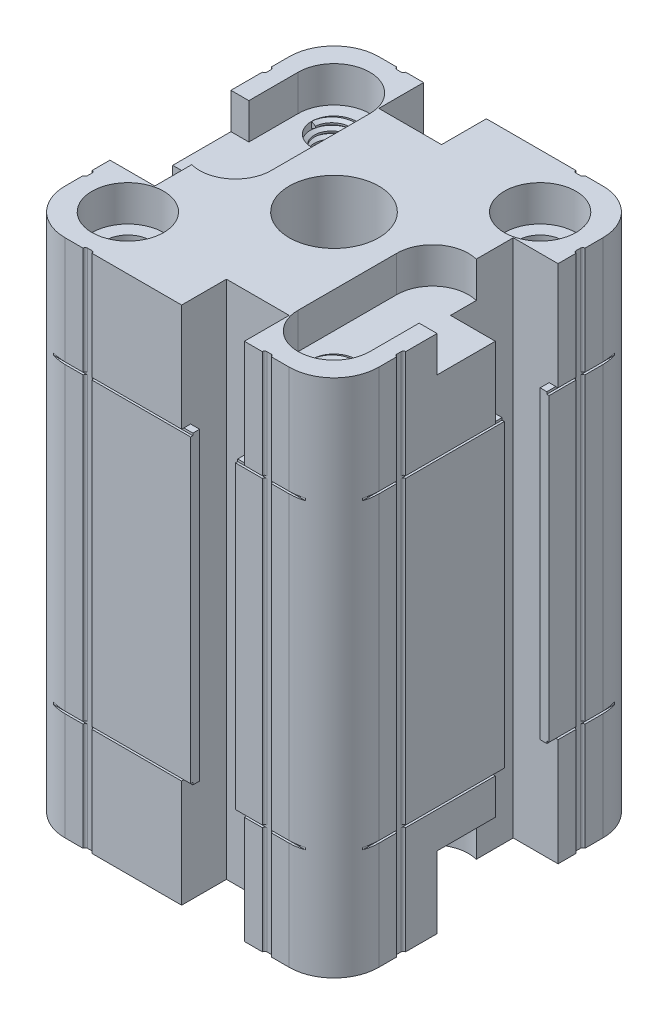
SolidWorks part; units mm, degrees
ref_plane "Front Plane" through (0, 0, 0) normal (0, 0, 1) x (1, 0, 0)
ref_plane "Top Plane" through (0, 0, 0) normal (0, 1, 0) x (1, 0, 0)
ref_plane "Right Plane" through (0, 0, 0) normal (1, 0, 0) x (0, 0, -1)
sketch "Sketch1" plane through (0, 0, 0) normal (0, 1, 0) x (1, 0, 0)
  line L1 (0, 0) -> (35, 0)
  line L2 (0, 0) -> (0, 35)
  line L3 (0, 35) -> (35, 35)
  line L4 (35, 0) -> (35, 35)
  dimension "D1" = 35
  dimension "D2" = 35
extrude "Boss-Extrude1" add sketch "Sketch1" along normal blind 58
sketch "Sketch2" plane through (0, 0, 0) normal (0, -1, 0) x (-1, 0, 0)
  line L0 (0, 0) -> (-35, 0) construction
  line L1 (0, 35) -> (0, 0) construction
  line L2 (-29, 6) -> (-29, 17) construction
  line L3 (-33, 6) -> (-33, 17)
  line L4 (-25, 6) -> (-25, 17)
  line L5 (-35, 0) -> (-35, 35) construction
  line L6 (-35, 35) -> (0, 35) construction
  line L7 (-6, 18) -> (-6, 29) construction
  line L8 (-10, 18) -> (-10, 29)
  line L9 (-2, 18) -> (-2, 29)
  circle A0 centre (-6, 6) radius 4
  circle A1 centre (-29, 29) radius 4
  arc A2 (-33, 6) -> (-25, 6) centre (-29, 6) ccw
  arc A3 (-25, 17) -> (-33, 17) centre (-29, 17) ccw
  arc A4 (-10, 18) -> (-2, 18) centre (-6, 18) ccw
  arc A5 (-2, 29) -> (-10, 29) centre (-6, 29) ccw
  point P10 (-29, 11.5)
  point P21 (-6, 23.5)
  dimension "D1" = 8
  dimension "D4" = 4
  dimension "D5" = 11
  dimension "D10" = 4
  dimension "D11" = 6
  dimension "D2" = 6
  dimension "D3" = 6
  dimension "D6" = 6
  dimension "D7" = 6
  dimension "D8" = 6
  dimension "D9" = 11
extrude "Cut-Extrude1" cut sketch "Sketch2" against normal blind 8
sketch "Sketch3" plane through (0, 0, 0) normal (0, -1, 0) x (-1, 0, 0)
  line L0 (0, 35) -> (0, 0) construction
  line L1 (-5, 23.5) -> (0, 23.5)
  line L2 (-5, 23.5) -> (-5, 14.127)
  line L3 (-5, 14.127) -> (0, 14.127)
  line L4 (0, 23.5) -> (0, 14.127)
  line L5 (-2, 18) -> (-2, 29) construction
  line L6 (-35, 20.873) -> (-30, 20.873)
  line L7 (-35, 20.873) -> (-35, 11.5)
  line L8 (-35, 11.5) -> (-30, 11.5)
  line L9 (-30, 20.873) -> (-30, 11.5)
  line L10 (-35, 0) -> (-35, 35) construction
  line L11 (-33, 17) -> (-33, 6) construction
  arc A2 (-25, 17) -> (-33, 17) centre (-29, 17) ccw construction
  arc A3 (-10, 18) -> (-2, 18) centre (-6, 18) ccw construction
  point P13 (-2, 23.5)
  point P25 (-32.5, 20.873)
  point P34 (-33, 11.5)
  dimension "D1" = 5
  dimension "D2" = 5
extrude "Cut-Extrude2" cut sketch "Sketch3" against normal up to surface (8 mm away) up to face at (6, 8, -23.5)
sketch "Sketch5" plane through (0, 0, 0) normal (0, -1, 0) x (1, 0, 0)
  line L0 (35, -20.873) -> (35, -35) construction
  line L1 (5, -17) -> (0, -17)
  line L2 (5, -17) -> (5, -10)
  line L3 (5, -10) -> (0, -10)
  line L4 (0, -17) -> (0, -10)
  line L5 (30, -18) -> (35, -18)
  line L6 (30, -18) -> (30, -25)
  line L7 (30, -25) -> (35, -25)
  line L8 (35, -18) -> (35, -25)
  line L9 (0, 0) -> (35, 0) construction
  line L10 (18, 0) -> (25, 0)
  line L11 (18, 0) -> (18, -5)
  line L12 (18, -5) -> (25, -5)
  line L13 (25, 0) -> (25, -5)
  line L14 (35, -35) -> (0, -35) construction
  line L15 (10, -35) -> (17, -35)
  line L16 (10, -35) -> (10, -30)
  line L17 (10, -30) -> (17, -30)
  line L18 (17, -35) -> (17, -30)
  circle A0 centre (6, -6) radius 4 construction
  circle A1 centre (29, -29) radius 4 construction
  dimension "D1" = 7
  dimension "D2" = 7
  dimension "D3" = 5
  dimension "D4" = 7
  dimension "D5" = 10
  dimension "D6" = 7
  dimension "D7" = 5
  dimension "D8" = 10
extrude "Cut-Extrude3" cut sketch "Sketch5" against normal blind 12
sketch "Sketch6" plane through (0, 12, 0) normal (0, -1, 0) x (1, 0, 0)
  line L6 (0, -16) -> (1, -16)
  line L7 (0, -10) -> (0, -17) construction
  line L8 (1, -16) -> (1, -17)
  line L9 (0, -17) -> (5, -17) construction
  line L10 (1, -17) -> (5, -17)
  line L11 (5, -17) -> (5, -10)
  line L12 (5, -10) -> (1, -10)
  line L13 (5, -10) -> (0, -10) construction
  line L14 (1, -10) -> (1, -11)
  line L15 (1, -11) -> (0, -11)
  line L16 (0, -11) -> (0, -16)
  line L17 (19, 0) -> (19, -1)
  line L18 (25, 0) -> (18, 0) construction
  line L19 (19, -1) -> (18, -1)
  line L20 (18, 0) -> (18, -5) construction
  line L21 (18, -1) -> (18, -5)
  line L22 (18, -5) -> (25, -5)
  line L23 (25, -5) -> (25, -1.01)
  line L24 (25, -5) -> (25, 0) construction
  line L25 (25, -1.01) -> (24, -1.01)
  line L26 (24, -1.01) -> (24, 0)
  line L27 (24, 0) -> (19, 0)
  line L28 (35, -19) -> (34, -19)
  line L29 (35, -25) -> (35, -18) construction
  line L30 (34, -19) -> (34, -18)
  line L31 (35, -18) -> (30, -18) construction
  line L32 (34, -18) -> (30, -18)
  line L33 (30, -18) -> (30, -25)
  line L34 (30, -25) -> (34, -25)
  line L35 (30, -25) -> (35, -25) construction
  line L36 (34, -25) -> (34, -24)
  line L37 (34, -24) -> (35, -24)
  line L38 (35, -24) -> (35, -19)
  line L39 (11, -35) -> (11, -34)
  line L40 (10, -35) -> (17, -35) construction
  line L41 (11, -34) -> (10, -34)
  line L42 (10, -30) -> (10, -35) construction
  line L43 (10, -34) -> (10, -30)
  line L44 (10, -30) -> (17, -30)
  line L45 (17, -30) -> (17, -34)
  line L46 (17, -35) -> (17, -30) construction
  line L47 (17, -34) -> (16, -34)
  line L48 (16, -34) -> (16, -35)
  line L49 (16, -35) -> (11, -35)
  dimension "D1" = 1
  dimension "D2" = 1
  dimension "D3" = 1
  dimension "D4" = 1
extrude "Cut-Extrude4" cut sketch "Sketch6" against normal blind 34
sketch "Sketch7" plane through (0, 58, 0) normal (0, 1, 0) x (1, 0, 0)
  line L0 (6, 29) -> (6, 18) construction
  line L1 (10, 29) -> (10, 18)
  line L2 (2, 29) -> (2, 18)
  line L3 (29, 17) -> (29, 6) construction
  line L4 (33, 17) -> (33, 6)
  line L5 (25, 17) -> (25, 6)
  arc A2 (10, 29) -> (2, 29) centre (6, 29) ccw
  arc A6 (2, 18) -> (10, 18) centre (6, 18) ccw
  circle A8 centre (29, 29) radius 4
  arc A9 (10, 29) -> (2, 29) centre (6, 29) ccw construction
  arc A10 (33, 17) -> (25, 17) centre (29, 17) ccw
  arc A11 (25, 6) -> (33, 6) centre (29, 6) ccw
  arc A12 (33, 17) -> (25, 17) centre (29, 17) ccw construction
  circle A13 centre (6, 6) radius 4
  point P4 (6, 23.5)
  point P14 (29, 11.5)
extrude "Cut-Extrude5" cut sketch "Sketch7" against normal blind 4
sketch "Sketch9" plane through (0, 58, 0) normal (0, 1, 0) x (1, 0, 0)
  line L1 (0, 23.5) -> (5, 23.5)
  line L2 (0, 23.5) -> (0, 14.127)
  line L3 (0, 14.127) -> (5, 14.127)
  line L4 (5, 23.5) -> (5, 14.127)
  line L5 (35, 20.873) -> (30, 20.873)
  line L6 (35, 20.873) -> (35, 11.5)
  line L7 (35, 11.5) -> (30, 11.5)
  line L8 (30, 20.873) -> (30, 11.5)
extrude "Cut-Extrude7" cut sketch "Sketch9" against normal up to surface (4 mm away) up to face at (6, 54, -23.5)
sketch "Sketch10" plane through (0, 58, 0) normal (0, 1, 0) x (1, 0, 0)
  line L1 (10, 30) -> (17, 30)
  line L2 (10, 30) -> (10, 35)
  line L3 (10, 35) -> (17, 35)
  line L4 (17, 30) -> (17, 35)
  line L5 (35, 25) -> (30, 25)
  line L6 (35, 25) -> (35, 18)
  line L7 (35, 18) -> (30, 18)
  line L8 (30, 25) -> (30, 18)
  line L9 (5, 10) -> (0, 10)
  line L10 (5, 10) -> (5, 17)
  line L11 (5, 17) -> (0, 17)
  line L12 (0, 10) -> (0, 17)
  line L13 (25, 5) -> (18, 5)
  line L14 (25, 5) -> (25, 0)
  line L15 (25, 0) -> (18, 0)
  line L16 (18, 5) -> (18, 0)
extrude "Cut-Extrude8" cut sketch "Sketch10" against normal up to surface (12 mm away) up to face at (1.75, 46, -13.5)
sketch "Sketch11" plane through (0, 58, 0) normal (0, 1, 0) x (1, 0, 0)
  line L0 (10, 35) -> (0, 35) construction
  line L1 (7, 35) -> (8, 35)
  line L2 (7, 35) -> (7, 34.75)
  line L3 (7, 34.75) -> (8, 34.75)
  line L4 (8, 35) -> (8, 34.75)
  line L5 (0, 35) -> (0, 23.5) construction
  line L6 (35, 35) -> (17, 35) construction
  line L7 (27, 35) -> (28, 35)
  line L8 (27, 35) -> (27, 34.75)
  line L9 (27, 34.75) -> (28, 34.75)
  line L10 (28, 35) -> (28, 34.75)
  line L11 (35, 25) -> (35, 35) construction
  line L12 (35, 0) -> (35, 11.5) construction
  line L13 (35, 28) -> (34.75, 28)
  line L14 (35, 28) -> (35, 27)
  line L15 (35, 27) -> (34.75, 27)
  line L16 (34.75, 28) -> (34.75, 27)
  line L17 (35, 8) -> (34.75, 8)
  line L18 (35, 8) -> (35, 7)
  line L19 (35, 7) -> (34.75, 7)
  line L20 (34.75, 8) -> (34.75, 7)
  line L21 (25, 0) -> (35, 0) construction
  line L22 (27, 0) -> (28, 0)
  line L23 (27, 0) -> (27, 0.25)
  line L24 (27, 0.25) -> (28, 0.25)
  line L25 (28, 0) -> (28, 0.25)
  line L26 (0, 0) -> (18, 0) construction
  line L27 (8, 0) -> (7, 0)
  line L28 (8, 0) -> (8, 0.25)
  line L29 (8, 0.25) -> (7, 0.25)
  line L30 (7, 0) -> (7, 0.25)
  line L31 (0, 10) -> (0, 0) construction
  line L32 (0, 8) -> (0.25, 8)
  line L33 (0, 8) -> (0, 7)
  line L34 (0, 7) -> (0.25, 7)
  line L35 (0.25, 8) -> (0.25, 7)
  line L36 (10, 35) -> (0, 35) construction
  line L37 (0, 28) -> (0.25, 28)
  line L38 (0, 28) -> (0, 27)
  line L39 (0, 27) -> (0.25, 27)
  line L40 (0.25, 28) -> (0.25, 27)
  dimension "D1" = 7
  dimension "D2" = 1
  dimension "D3" = 0.25
  dimension "D4" = 7
  dimension "D5" = 7
  dimension "D6" = 7
  dimension "D7" = 7
  dimension "D8" = 7
  dimension "D9" = 7
  dimension "D10" = 7
extrude "Cut-Extrude9" cut sketch "Sketch11" against normal through all
fillet "Fillet2" radius 0.25 16 edges at (0.25, 29, -7) (0.25, 29, -8) (7, 29, -0.25) (8, 29, -0.25) (28, 29, -0.25) (27, 29, -0.25) (34.75, 29, -8) (34.75, 29, -7) (34.75, 29, -27) (34.75, 29, -28) (27, 29, -34.75) (28, 29, -34.75) (7, 29, -34.75) (8, 29, -34.75) (0.25, 29, -27) (0.25, 29, -28)
sketch "Sketch12" plane through (0, 0, 0) normal (-1, 0, 0) x (0, 0, 1)
  line L0 (-35, 58) -> (-35, 0) construction
  line L1 (-35, 12.25) -> (-34.75, 12.25)
  line L2 (-35, 12.25) -> (-35, 12)
  line L3 (-35, 12) -> (-34.75, 12)
  line L4 (-34.75, 12.25) -> (-34.75, 12)
  line L5 (0, 58) -> (0, 0) construction
  line L6 (0, 12.25) -> (-0.25, 12.25)
  line L7 (0, 12.25) -> (0, 12)
  line L8 (0, 12) -> (-0.25, 12)
  line L9 (-0.25, 12.25) -> (-0.25, 12)
  line L10 (-35, 0) -> (-28, 0) construction
  line L11 (-7, 0) -> (0, 0) construction
  line L12 (-35, 58) -> (-28, 58) construction
  line L13 (-35, 46) -> (-34.75, 46)
  line L14 (-35, 46) -> (-35, 45.75)
  line L15 (-35, 45.75) -> (-34.75, 45.75)
  line L16 (-34.75, 46) -> (-34.75, 45.75)
  line L17 (0, 46) -> (-0.25, 46)
  line L18 (0, 46) -> (0, 45.75)
  line L19 (0, 45.75) -> (-0.25, 45.75)
  line L20 (-0.25, 46) -> (-0.25, 45.75)
  line L21 (-7, 58) -> (0, 58) construction
  dimension "D1" = 0.25
  dimension "D2" = 0.25
  dimension "D3" = 0.25
  dimension "D4" = 0.25
  dimension "D5" = 12
  dimension "D6" = 12
  dimension "D7" = 0.25
  dimension "D8" = 0.25
  dimension "D9" = 0.25
  dimension "D10" = 0.25
  dimension "D11" = 12
  dimension "D12" = 12
fillet "Fillet4" radius 5 4 edges at (35, 29, 0) (0, 29, 0) (35, 29, -35) (0, 29, -35)
extrude "Cut-Extrude12" cut sketch "Sketch12" against normal through all
sketch "Sketch14" plane through (0, 0, 0) normal (0, 0, 1) x (1, 0, 0)
  line L0 (35, 58) -> (35, 0) construction
  line L1 (0, 46) -> (0.25, 46)
  line L2 (0, 46) -> (0, 45.75)
  line L3 (0, 45.75) -> (0.25, 45.75)
  line L4 (0.25, 46) -> (0.25, 45.75)
  line L5 (35, 46) -> (34.75, 46)
  line L6 (35, 46) -> (35, 45.75)
  line L7 (35, 45.75) -> (34.75, 45.75)
  line L8 (34.75, 46) -> (34.75, 45.75)
  line L9 (0, 12.25) -> (0, 12) construction
  line L10 (0, 12.25) -> (0.25, 12.25)
  line L11 (0, 12.25) -> (0, 12)
  line L12 (0, 12) -> (0.25, 12)
  line L13 (0.25, 12.25) -> (0.25, 12)
  line L14 (0, 12.25) -> (0, 12) construction
  line L16 (35, 12.25) -> (34.75, 12.25)
  line L17 (35, 12.25) -> (35, 12)
  line L18 (35, 12) -> (34.75, 12)
  line L19 (34.75, 12.25) -> (34.75, 12)
  dimension "D1" = 0.25
  dimension "D2" = 0.25
  dimension "D3" = 0.25
  dimension "D4" = 0.25
  dimension "D5" = 0.25
  dimension "D6" = 0.25
  dimension "D7" = 0.25
  dimension "D8" = 0.25
extrude "Cut-Extrude13" cut sketch "Sketch14" against normal through all
sketch "Sketch15" plane through (0, 8, 0) normal (0, -1, 0) x (-1, 0, 0)
  circle A0 centre (-6, 6) radius 2.5
  circle A1 centre (-29, 29) radius 2.5
  circle A3 centre (-29, 6) radius 2.5
  circle A4 centre (-6, 29) radius 2.5
  dimension "D1" = 5
extrude "Cut-Extrude14" cut sketch "Sketch15" against normal up to vertex (4 mm away) up to point (0.25, 12, -3.4388)
thread "Thread2" pitch 0.8 method extrude profile "Thread Profile2" start angle 0, offset 0, length 0, pitch 0.8, diameter 5
ref_plane "Plane2" through (31.5, 8, -6) normal (0, 0, 1) x (1, 0, 0)
sketch "Thread Profile2" plane through (31.5, 8, -6) normal (0, 0, 1) x (1, 0, 0)
  line L0 (0, 0) -> (0, 0.8) construction
  line L11 (0, 0) -> (0, 0.7)
  line L12 (0, 0.7) -> (-0.433, 0.45)
  line L13 (-0.433, 0.45) -> (-0.433, 0.25)
  line L15 (-0.433, 0.25) -> (0, 0)
  line L17 (-0.433, 0.35) -> (0, 0.35) construction
  point P2 (0, 0)
  dimension "Pitch" = 0.8
  dimension "Profile_Angle" = 60
  dimension "Profile_Land" = 0.2
  dimension "Profile_Height" = 0.433
thread "Thread3" pitch 0.8 method extrude profile "Thread Profile3" start angle 0, offset 0, length 0, pitch 0.8, diameter 5
ref_plane "Plane3" through (8.5, 8, -29) normal (0, 0, 1) x (1, 0, 0)
sketch "Thread Profile3" plane through (8.5, 8, -29) normal (0, 0, 1) x (1, 0, 0)
  line L0 (0, 0) -> (0, 0.8) construction
  line L11 (0, 0) -> (0, 0.7)
  line L12 (0, 0.7) -> (-0.433, 0.45)
  line L13 (-0.433, 0.45) -> (-0.433, 0.25)
  line L15 (-0.433, 0.25) -> (0, 0)
  line L17 (-0.433, 0.35) -> (0, 0.35) construction
  point P2 (0, 0)
  dimension "Pitch" = 0.8
  dimension "Profile_Angle" = 60
  dimension "Profile_Land" = 0.2
  dimension "Profile_Height" = 0.433
sketch "Sketch24" plane through (0, 54, 0) normal (0, 1, 0) x (1, 0, 0)
  circle A0 centre (6, 29) radius 2.5
  circle A1 centre (29, 29) radius 2.5
  circle A2 centre (6, 6) radius 2.5
  circle A3 centre (29, 6) radius 2.5
  dimension "D1" = 5
extrude "Cut-Extrude15" cut sketch "Sketch24" against normal up to vertex (8 mm away) up to point (34.75, 46, -3.4388)
thread "Thread5" pitch 0.8 method extrude profile "Thread Profile5" start angle 0, offset 0, length 0, pitch 0.8, diameter 5
ref_plane "Plane5" through (26.5, 54, -6) normal (0, 0, 1) x (-1, 0, 0)
sketch "Thread Profile5" plane through (26.5, 54, -6) normal (0, 0, 1) x (-1, 0, 0)
  line L0 (0, 0) -> (0, 0.8) construction
  line L11 (0, 0) -> (0, 0.7)
  line L12 (0, 0.7) -> (-0.433, 0.45)
  line L13 (-0.433, 0.45) -> (-0.433, 0.25)
  line L15 (-0.433, 0.25) -> (0, 0)
  line L17 (-0.433, 0.35) -> (0, 0.35) construction
  point P2 (0, 0)
  dimension "Pitch" = 0.8
  dimension "Profile_Angle" = 60
  dimension "Profile_Land" = 0.2
  dimension "Profile_Height" = 0.433
thread "Thread8" pitch 0.8 method extrude profile "Thread Profile8" start angle 0, offset 0, length 0, pitch 0.8, diameter 5
ref_plane "Plane8" through (3.5, 54, -29) normal (0, 0, 1) x (-1, 0, 0)
sketch "Thread Profile8" plane through (3.5, 54, -29) normal (0, 0, 1) x (-1, 0, 0)
  line L0 (0, 0) -> (0, 0.8) construction
  line L11 (0, 0) -> (0, 0.7)
  line L12 (0, 0.7) -> (-0.433, 0.45)
  line L13 (-0.433, 0.45) -> (-0.433, 0.25)
  line L15 (-0.433, 0.25) -> (0, 0)
  line L17 (-0.433, 0.35) -> (0, 0.35) construction
  point P2 (0, 0)
  dimension "Pitch" = 0.8
  dimension "Profile_Angle" = 60
  dimension "Profile_Land" = 0.2
  dimension "Profile_Height" = 0.433
sketch "Sketch33" plane through (0, 0, 0) normal (0, -1, 0) x (-1, 0, 0)
  circle A0 centre (-18, 18) radius 6
  dimension "D1" = 12
extrude "Cut-Extrude16" cut sketch "Sketch33" against normal blind 3
ref_plane "Plane9" through (0, 45.75, 0) normal (0, 1, 0) x (1, 0, 0)
sketch "Sketch34" plane through (0, 45.75, 0) normal (0, 1, 0) x (1, 0, 0)
  line L1 (26.5, 26.5) -> (8.5, 26.5)
  line L2 (26.5, 26.5) -> (26.5, 8.5)
  line L3 (26.5, 8.5) -> (8.5, 8.5)
  line L4 (8.5, 26.5) -> (8.5, 8.5)
  line L10 (0, 0) -> (0, 35) construction
  line L11 (0, 35) -> (35, 35) construction
  line L12 (35, 0) -> (35, 35) construction
  line L13 (0, 0) -> (35, 0) construction
  dimension "D1" = 8.5
  dimension "D2" = 8.5
  dimension "D3" = 8.5
  dimension "D4" = 8.5
extrude "Cut-Extrude17" cut sketch "Sketch34" against normal blind 25
sketch "Sketch35" plane through (0, 58, 0) normal (0, 1, 0) x (1, 0, 0)
  line L0 (27, 35) -> (17, 35) construction
  line L1 (0, 17) -> (0, 23.5) construction
  circle A0 centre (17.5, 17.5) radius 5
  dimension "D1" = 10
  dimension "D2" = 17.5
  dimension "D3" = 17.5
extrude "Cut-Extrude18" cut sketch "Sketch35" against normal up to surface (12.25 mm away) up to plane "Plane9"
extrude "Cut-Extrude19" cut sketch "Sketch15<3>" against normal through all contours A1 | A0
sketch "Sketch15<3>" plane through (0, 8, 0) normal (0, -1, 0) x (-1, 0, 0) same geometry as "Sketch15"
